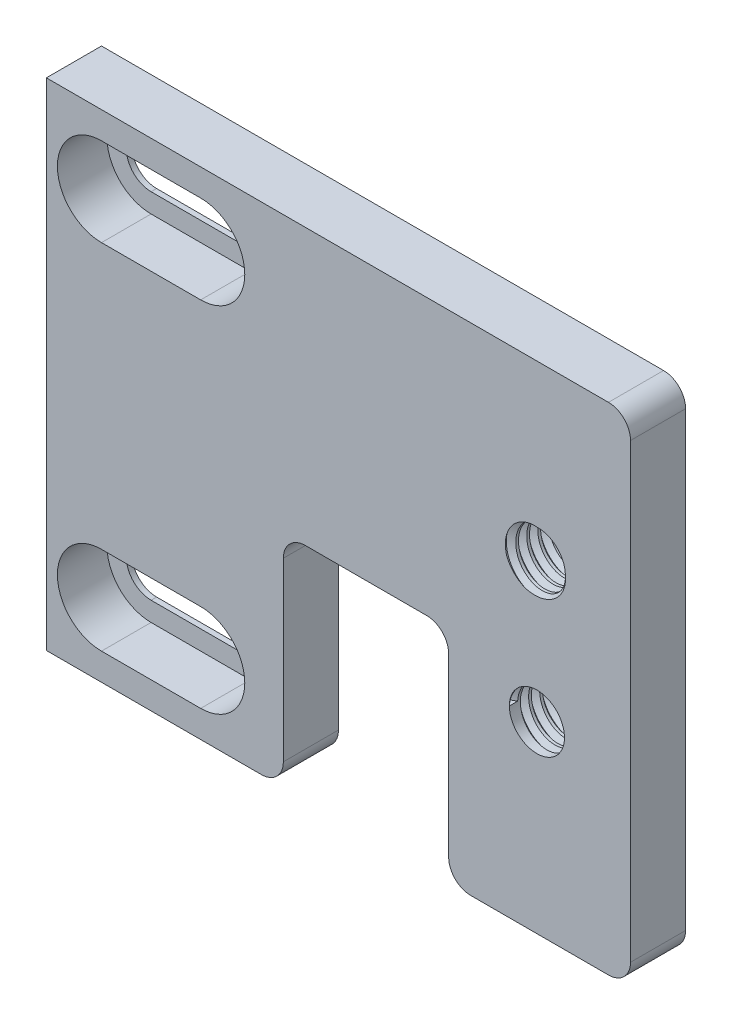
SolidWorks part; units mm, degrees
ref_plane "Front Plane" through (0, 0, 0) normal (0, 0, 1) x (1, 0, 0)
ref_plane "Top Plane" through (0, 0, 0) normal (0, 1, 0) x (1, 0, 0)
ref_plane "Right Plane" through (0, 0, 0) normal (1, 0, 0) x (0, 0, -1)
sketch "Sketch1" plane through (0, 0, 0) normal (0, 0, 1) x (1, 0, 0)
  line L0 (-34.2537, 0) -> (-34.2537, 45)
  line L1 (-34.2537, 45) -> (16.7463, 45)
  line L2 (18.7463, 43) -> (18.7463, 2)
  line L3 (16.7463, 0) -> (4.2463, 0)
  line L4 (2.2463, 2) -> (2.2463, 18)
  line L5 (0.2463, 20) -> (-10.7537, 20)
  line L6 (-12.7537, 18) -> (-12.7537, 2)
  line L7 (-14.7537, 0) -> (-34.2537, 0)
  arc A0 (16.7463, 45) -> (18.7463, 43) centre (16.7463, 43) cw
  arc A1 (18.7463, 2) -> (16.7463, 0) centre (16.7463, 2) cw
  arc A2 (4.2463, 0) -> (2.2463, 2) centre (4.2463, 2) cw
  arc A3 (-12.7537, 2) -> (-14.7537, 0) centre (-14.7537, 2) cw
  arc A4 (2.2463, 18) -> (0.2463, 20) centre (0.2463, 18) ccw
  arc A5 (-10.7537, 20) -> (-12.7537, 18) centre (-10.7537, 18) ccw
  point P11 (18.7463, 45)
  point P14 (18.7463, 0)
  point P17 (2.2463, 0)
  point P20 (-12.7537, 0)
  point P23 (2.2463, 20)
  point P26 (-12.7537, 20)
  dimension "D9" = 2
  dimension "D1" = 45
  dimension "D2" = 53
  dimension "D3" = 16.5
  dimension "D4" = 20
  dimension "D5" = 15
  dimension "D6" = 20
  dimension "D7" = 21.5
  dimension "D8" = 45
extrude "Boss-Extrude1" add sketch "Sketch1" along normal blind 5
sketch "Sketch2" plane through (0, 0, 5) normal (0, 0, 1) x (1, 0, 0)
  line L0 (-29.2537, 0) -> (-29.2537, 2.45) construction
  line L1 (-34.2537, 0) -> (-14.7537, 0) construction
  line L2 (-34.2537, 45) -> (-34.2537, 0) construction
  line L4 (16.7463, 45) -> (-34.2537, 45) construction
  line L6 (-29.2537, 13.2307) -> (-29.2537, 1.225) construction
  line L7 (-29.2537, 42.55) -> (-20.2537, 42.55)
  line L8 (-29.2537, 34.55) -> (-20.2537, 34.55)
  line L10 (-29.2537, 10.45) -> (-20.2537, 10.45)
  line L11 (-29.2537, 2.45) -> (-20.2537, 2.45)
  arc A1 (-29.2537, 10.45) -> (-29.2537, 2.45) centre (-29.2537, 6.45) ccw
  arc A2 (-29.2537, 42.55) -> (-29.2537, 34.55) centre (-29.2537, 38.55) ccw
  arc A3 (-20.2537, 42.55) -> (-20.2537, 34.55) centre (-20.2537, 38.55) cw
  arc A4 (-20.2537, 10.45) -> (-20.2537, 2.45) centre (-20.2537, 6.45) cw
  point P6 (-33.2537, 6.45)
  point P10 (-34.9056, 5.6882)
  dimension "D3" = 1
  dimension "D2" = 8
  dimension "D5" = 8
  dimension "D9" = 4
  dimension "D1" = 2.45
  dimension "D4" = 2.45
  dimension "D6" = 9
  dimension "D7" = 9
  dimension "D8" = 9
extrude "Cut-Extrude2" cut sketch "Sketch2" against normal blind 4.5
sketch "Sketch3" plane through (0, 0, 0.5) normal (0, 0, 1) x (1, 0, 0)
  line L0 (-29.2537, 4.2) -> (-29.2537, 8.7) construction
  line L1 (-29.2537, 8.7) -> (-20.2537, 8.7)
  line L2 (-29.2537, 4.2) -> (-20.2537, 4.2)
  line L3 (-34.2537, 22.5) -> (-5.8785, 22.5) construction
  line L4 (-34.2537, 45) -> (-34.2537, 0) construction
  line L5 (-29.2537, 40.8) -> (-20.2537, 40.8)
  line L6 (-29.2537, 36.3) -> (-20.2537, 36.3)
  arc A0 (-29.2537, 8.7) -> (-29.2537, 4.2) centre (-29.2537, 6.45) ccw
  arc A1 (-20.2537, 8.7) -> (-20.2537, 4.2) centre (-20.2537, 6.45) cw
  arc A2 (-20.2537, 36.3) -> (-20.2537, 40.8) centre (-20.2537, 38.55) ccw
  arc A3 (-29.2537, 36.3) -> (-29.2537, 40.8) centre (-29.2537, 38.55) cw
  dimension "D1" = 4.5
  dimension "D2" = 2.25
  dimension "D3" = 9
extrude "Cut-Extrude3" cut sketch "Sketch3" against normal through all
sketch "Sketch4" plane through (0, 0, 5) normal (0, 0, 1) x (1, 0, 0)
  line L0 (4.2463, 0) -> (16.7463, 0) construction
  line L1 (18.7463, 2) -> (18.7463, 43) construction
  line L2 (16.7463, 45) -> (-34.2537, 45) construction
  circle A0 centre (10.2563, 16.65) radius 2.5
  circle A1 centre (10.3363, 29.45) radius 2.5
  dimension "D1" = 5
  dimension "D2" = 5
  dimension "D3" = 16.65
  dimension "D4" = 8.49
  dimension "D5" = 15.55
  dimension "D6" = 8.41
extrude "Cut-Extrude4" cut sketch "Sketch4" against normal through all
thread "Thread3" pitch 1 method cut profile "Thread Profile3" start angle 0, offset 0, length 0, pitch 1, diameter 5
ref_plane "Plane3" through (12.8363, 29.45, 0) normal (0, -1, 0) x (1, 0, 0)
sketch "Thread Profile3" plane through (12.8363, 29.45, 0) normal (0, -1, 0) x (1, 0, 0)
  line L0 (0, 0) -> (0, 1) construction
  line L1 (0, 0) -> (0.5413, 0.3125)
  line L2 (0.5413, 0.3125) -> (0.5413, 0.4375)
  line L3 (0.5413, 0.4375) -> (0, 0.75)
  line L4 (0.5413, 0.375) -> (0, 0.375) construction
  line L11 (0, 0) -> (0, 0.75)
  point P2 (0, 0)
  dimension "Pitch" = 1
  dimension "Profile_Angle" = 60
  dimension "Profile_Land" = 0.125
  dimension "Profile_Height" = 0.5413
thread "Thread4" pitch 1 method cut profile "Thread Profile4" start angle 0, offset 0, length 0, pitch 1, diameter 5
ref_plane "Plane4" through (7.7563, 16.65, 5) normal (0, -1, 0) x (-1, 0, 0)
sketch "Thread Profile4" plane through (7.7563, 16.65, 5) normal (0, -1, 0) x (-1, 0, 0)
  line L0 (0, 0) -> (0, 1) construction
  line L1 (0, 0) -> (0.5413, 0.3125)
  line L2 (0.5413, 0.3125) -> (0.5413, 0.4375)
  line L3 (0.5413, 0.4375) -> (0, 0.75)
  line L4 (0.5413, 0.375) -> (0, 0.375) construction
  line L11 (0, 0) -> (0, 0.75)
  point P2 (0, 0)
  dimension "Pitch" = 1
  dimension "Profile_Angle" = 60
  dimension "Profile_Land" = 0.125
  dimension "Profile_Height" = 0.5413
